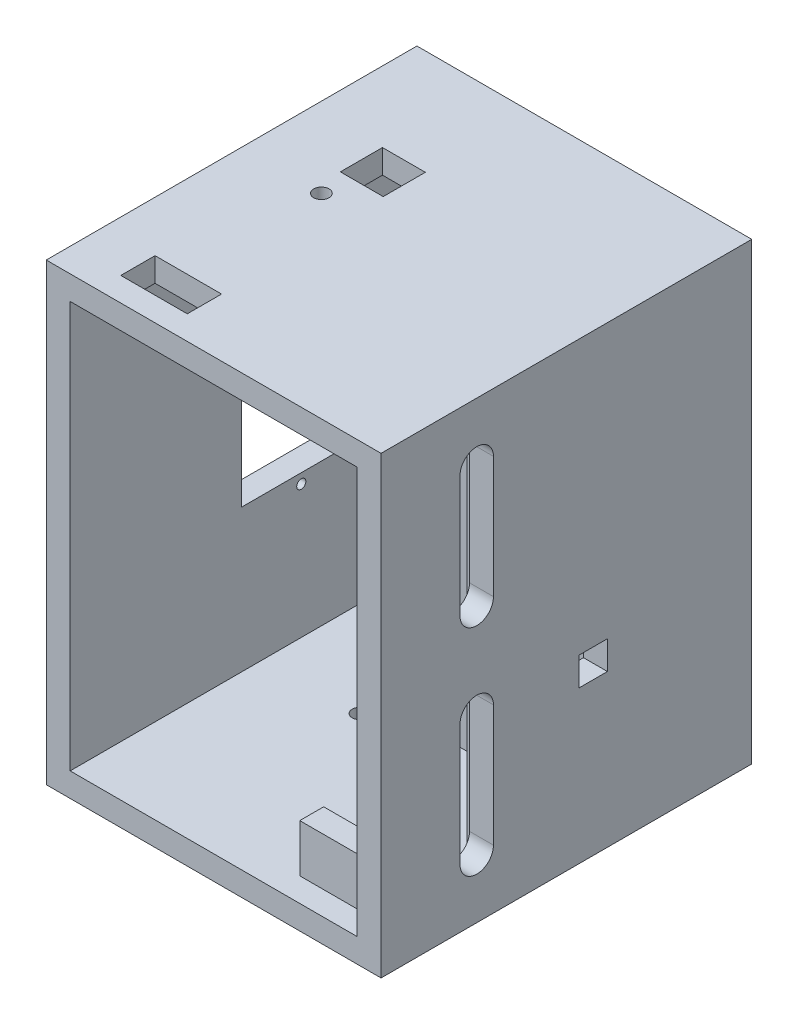
SolidWorks part; units mm, degrees
ref_plane "Front Plane" through (0, 0, 0) normal (0, 0, 1) x (1, 0, 0)
ref_plane "Top Plane" through (0, 0, 0) normal (0, 1, 0) x (1, 0, 0)
ref_plane "Right Plane" through (0, 0, 0) normal (1, 0, 0) x (0, 0, -1)
sketch "Sketch1" plane through (0, 0, 0) normal (0, 0, 1) x (1, 0, 0)
  line L1 (-17.5349, 30.527) -> (52.4651, 30.527)
  line L2 (-17.5349, 30.527) -> (-17.5349, -64.473)
  line L3 (-17.5349, -64.473) -> (52.4651, -64.473)
  line L4 (47.4651, 25.527) -> (-12.5349, 25.527)
  line L5 (-12.5349, 25.527) -> (-12.5349, -59.473)
  line L6 (-12.5349, -59.473) -> (47.4651, -59.473)
  line L7 (47.4651, -59.473) -> (47.4651, 25.527)
  line L8 (47.4651, 25.527) -> (-12.5349, 25.527)
  line L9 (-12.5349, 25.527) -> (-12.5349, -59.473)
  line L10 (-12.5349, -59.473) -> (47.4651, -59.473)
  line L11 (47.4651, -59.473) -> (47.4651, 25.527)
  line L12 (52.4651, 30.527) -> (52.4651, -64.473)
  line L13 (-17.5349, 30.527) -> (52.4651, -64.473) construction
  line L14 (-17.5349, -64.473) -> (52.4651, 30.527) construction
  point P2 (17.4651, -16.973)
  dimension "D2" = 5
  dimension "D3" = 5
  dimension "D4" = 5
  dimension "D5" = 5
  dimension "D1" = 0
extrude "Boss-Extrude1" add sketch "Sketch1" against normal blind 75 contours L12 L1 L2 L3 L11 L10 L9 L8 region at (17.4651, 29.347, 0)
sketch "Sketch2" plane through (-17.5349, 0, 0) normal (-1, 0, 0) x (0, 0, 1)
  line L0 (-59.8109, -17.0822) -> (-59.8109, -28.6392) construction
  line L1 (-60.8109, -29.6392) -> (-35.8239, -29.6392)
  line L2 (-60.8109, -29.6392) -> (-60.8109, -4.5252)
  line L3 (-60.8109, -4.5252) -> (-35.8239, -4.5252)
  line L4 (-35.8239, -29.6392) -> (-35.8239, -4.5252)
  line L5 (-59.8109, -28.6392) -> (-36.8239, -28.6392) construction
  line L6 (-36.8239, -5.5252) -> (-59.8109, -5.5252) construction
  line L7 (-36.8239, -17.0822) -> (-36.8239, -5.5252) construction
  circle A0 centre (-48.3174, -2.4772) radius 0.9525 construction
  circle A1 centre (-48.3174, -31.6872) radius 0.9525 construction
  circle A2 centre (-48.3174, -2.4772) radius 0.9525
  circle A3 centre (-48.3174, -31.6872) radius 0.9525
  dimension "D1" = 1
  dimension "D2" = 1
  dimension "D3" = 1
  dimension "D4" = 1
extrude "Cut-Extrude1" cut sketch "Sketch2" against normal blind 27
sketch "Sketch3" plane through (0, 30.527, 0) normal (0, 1, 0) x (1, 0, 0)
  line L0 (-1.7529, 47.707) -> (5.2067, 47.707) construction
  line L1 (-1.7529, 47.707) -> (5.2067, 47.707)
  line L2 (5.2067, 54.5142) -> (-1.7529, 54.5142) construction
  line L3 (-2.7529, 46.707) -> (6.2067, 46.707)
  line L4 (-2.7529, 46.707) -> (-2.7529, 55.5142)
  line L5 (-2.7529, 55.5142) -> (6.2067, 55.5142)
  line L6 (6.2067, 46.707) -> (6.2067, 55.5142)
  line L7 (-1.7529, 54.5142) -> (-1.7529, 47.707) construction
  line L8 (5.2067, 47.707) -> (5.2067, 54.5142) construction
  line L9 (4.45, 12.1628) -> (-4.45, 12.1628) construction
  line L10 (4.45, 12.1628) -> (-4.45, 12.1628)
  line L11 (47.4651, 0) -> (-12.5349, 0) construction
  line L12 (6.95, 12.1628) -> (-6.95, 12.1628)
  line L13 (6.95, 12.1628) -> (6.95, 5)
  line L14 (6.95, 5) -> (-6.95, 5)
  line L15 (-6.95, 12.1628) -> (-6.95, 5)
  circle A0 centre (-0.8512, 40.8363) radius 1.6129 construction
  circle A1 centre (-0.8512, 40.8363) radius 1.6129
  dimension "D1" = 1
  dimension "D2" = 1
  dimension "D3" = 1
  dimension "D4" = 1
  dimension "D5" = 5
  dimension "D6" = 0
  dimension "D7" = 2.5
  dimension "D8" = 2.5
extrude "Cut-Extrude2" cut sketch "Sketch3" against normal blind 27 contours L3 L6 L5 L4 | A1 | L12 L15 L14 L13 L10 region at (1.7269, 30.527, -51.1106) region at (0, 30.527, -8.5814) region at (-0.8512, 30.527, -40.8363)
sketch "Sketch4" plane through (52.4651, 0, 0) normal (1, 0, 0) x (0, 0, -1)
  line L0 (46.3258, -31.6429) -> (46.3258, -27.7059) construction
  line L1 (47.3258, -32.6429) -> (41.3888, -32.6429)
  line L2 (47.3258, -32.6429) -> (47.3258, -26.7059)
  line L3 (47.3258, -26.7059) -> (41.3888, -26.7059)
  line L4 (41.3888, -32.6429) -> (41.3888, -26.7059)
  line L5 (42.3888, -31.6429) -> (46.3258, -31.6429) construction
  line L6 (46.3258, -27.7059) -> (42.3888, -27.7059) construction
  line L7 (42.3888, -27.7059) -> (42.3888, -31.6429) construction
  dimension "D1" = 1
  dimension "D2" = 1
  dimension "D3" = 1
  dimension "D4" = 1
extrude "Cut-Extrude3" cut sketch "Sketch4" against normal blind 27 contours L3 L4 L1 L2
sketch "Sketch5" plane through (47.4651, 0, 0) normal (-1, 0, 0) x (0, 0, 1)
  line L0 (-38.4772, 5.2125) -> (-38.4772, -47.9243) construction
  line L1 (-5, 25.527) -> (-5, -59.473) construction
  line L2 (-38.4772, 5.2125) -> (-38.4772, -47.9243)
  line L3 (-5, 25.527) -> (-5, -59.473)
  line L5 (-38.4772, -47.9243) -> (-33.4772, -47.9243)
  line L6 (-38.4772, -47.9243) -> (-38.4772, 5.2125)
  line L7 (-38.4772, 5.2125) -> (-33.4772, 5.2125)
  line L8 (-33.4772, -47.9243) -> (-33.4772, 5.2125)
  line L9 (-5, -59.473) -> (-10, -59.473)
  line L10 (-5, -59.473) -> (-5, -49.473)
  line L11 (-5, -49.473) -> (-10, -49.473)
  line L12 (-10, -59.473) -> (-10, -49.473)
  line M8 (-75, -59.473) -> (0, -59.473)
  dimension "D1" = 5
  dimension "D2" = 5
  dimension "D3" = 10
extrude "Boss-Extrude2" add sketch "Sketch5" along normal blind 17 contours L12 L3 L11 M8 | L5 L8 L7 L2 region at (47.4651, -21.3559, -35.9772) region at (47.4651, -54.473, -7.5)
sketch "Sketch6" plane through (0, 0, -38.4772) normal (0, 0, -1) x (-1, 0, 0)
  line L0 (-35.0699, 5.2125) -> (-35.0699, -47.9243) construction
  line L1 (-35.0699, -32.9243) -> (-30.4651, -32.9243)
  line L2 (-35.0699, -32.9243) -> (-35.0699, -9.7875)
  line L3 (-35.0699, -9.7875) -> (-30.4651, -9.7875)
  line L4 (-30.4651, -32.9243) -> (-30.4651, -9.7875)
  line L5 (-30.4651, 5.2125) -> (-30.4651, -47.9243) construction
  line L6 (-30.4651, -47.9243) -> (-47.4651, -47.9243) construction
  line L7 (-30.4651, 5.2125) -> (-47.4651, 5.2125) construction
  dimension "D1" = 15
  dimension "D2" = 15
extrude "Boss-Extrude3" add sketch "Sketch6" along normal blind 17
sketch "Sketch7" plane through (0, 0, -10) normal (0, 0, -1) x (-1, 0, 0)
  circle A0 centre (-43.6551, -55.663) radius 1.27 construction
  circle A1 centre (-43.6551, -55.663) radius 1.27
extrude "Cut-Extrude4" cut sketch "Sketch7" against normal blind 17
sketch "Sketch8" plane through (0, -64.473, 0) normal (0, -1, 0) x (1, 0, 0)
  circle A0 centre (7.3496, -49.5601) radius 5.969 construction
  circle A1 centre (7.3496, -40.6701) radius 1.5875 construction
  circle A2 centre (7.3496, -49.5601) radius 5.969
  circle A3 centre (7.3496, -40.6701) radius 1.5875
  circle A4 centre (7.3496, -49.5601) radius 6.469
  dimension "D1" = 0.5
extrude "Cut-Extrude5" cut sketch "Sketch8" against normal blind 17 contours A2 | A3 region at (7.3496, -64.473, -49.5601) region at (7.3496, -64.473, -40.6701)
sketch "Sketch9" plane through (0, 0, -75) normal (0, 0, -1) x (-1, 0, 0)
  line L4 (-52.4651, 30.527) -> (-52.4651, -64.473)
  line L5 (-52.4651, -64.473) -> (17.5349, -64.473)
  line L6 (17.5349, -64.473) -> (17.5349, 30.527)
  line L7 (17.5349, 30.527) -> (-52.4651, 30.527)
  line L8 (-52.4651, 30.527) -> (-52.4651, -64.473)
  line L9 (-52.4651, -64.473) -> (17.5349, -64.473)
  line L10 (17.5349, -64.473) -> (17.5349, 30.527)
  line L11 (17.5349, 30.527) -> (-52.4651, 30.527)
  dimension "D1" = 0
extrude "Boss-Extrude4" add sketch "Sketch9" along normal mid plane 5
sketch "Sketch10" plane through (0, 0, -77.5) normal (0, 0, -1) x (-1, 0, 0)
  circle A0 centre (-19.6135, 13.0233) radius 4.572 construction
  circle A1 centre (-19.6135, 0.9583) radius 4.572 construction
  circle A2 centre (-19.6135, -11.1067) radius 4.572 construction
  circle A3 centre (-27.3605, -31.6172) radius 1.778 construction
  circle A4 centre (-11.8665, -31.6172) radius 1.778 construction
  circle A5 centre (-19.6135, 13.0233) radius 4.572
  circle A6 centre (-19.6135, 0.9583) radius 4.572
  circle A7 centre (-19.6135, -11.1067) radius 4.572
  circle A8 centre (-27.3605, -31.6172) radius 1.778
  circle A9 centre (-11.8665, -31.6172) radius 1.778
  circle A10 centre (-19.6135, -11.1067) radius 5.572
  circle A11 centre (-19.6135, 0.9583) radius 5.572
  circle A12 centre (-19.6135, 13.0233) radius 5.572
  dimension "D1" = 1
  dimension "D2" = 1
  dimension "D3" = 1
extrude "Cut-Extrude7" cut sketch "Sketch10" against normal blind 24 contours A5 | A12 A5 | A6 | A11 A6 | A9 | A10 | A8 region at (19.6135, 13.0233, -77.5) region at (19.6135, 0.9583, -77.5) region at (11.8665, -31.6172, -77.5) region at (25.0279, 0.9583, -77.5) region at (25.0279, 13.0233, -77.5)
sketch "Sketch11" plane through (52.4651, 0, 0) normal (1, 0, 0) x (0, 0, -1)
  line L0 (20, 18.227) -> (20, -7.173) construction
  line L1 (23.5, 18.227) -> (23.5, -7.173)
  line L2 (16.5, 18.227) -> (16.5, -7.173)
  line L3 (77.5, -16.973) -> (55.4772, -16.973) construction
  line L4 (77.5, 30.527) -> (77.5, -64.473) construction
  line L5 (55.4772, -9.7875) -> (55.4772, -32.9243) construction
  line L6 (0, 30.527) -> (0, -64.473) construction
  line L7 (77.5, 30.527) -> (0, 30.527) construction
  line L8 (20, -52.173) -> (20, -26.773) construction
  line L9 (23.5, -52.173) -> (23.5, -26.773)
  line L10 (16.5, -52.173) -> (16.5, -26.773)
  arc A0 (23.5, 18.227) -> (16.5, 18.227) centre (20, 18.227) ccw
  arc A1 (16.5, -7.173) -> (23.5, -7.173) centre (20, -7.173) ccw
  arc A2 (23.5, -52.173) -> (16.5, -52.173) centre (20, -52.173) cw
  arc A3 (16.5, -26.773) -> (23.5, -26.773) centre (20, -26.773) cw
  point P2 (20, 5.527)
  point P13 (0, 0)
  point P20 (20, -39.473)
  dimension "D1" = 3.5
  dimension "D2" = 25.4
  dimension "D3" = 20
  dimension "D4" = 25
extrude "Cut-Extrude8" cut sketch "Sketch11" against normal blind 10
sketch "Sketch12" plane through (47.4651, 0, 0) normal (-1, 0, 0) x (0, 0, 1)
  line L0 (-72.5, 25.527) -> (0, 25.527) construction
  line L2 (-25.4206, -10.366) -> (-25.4206, 25.527)
  line L3 (-25.4206, 25.527) -> (-30.4206, 25.527)
  line L5 (-72.5, -59.473) -> (-10, -59.473) construction
  line L6 (-30.4206, 25.527) -> (-25.4206, 25.527)
  line L7 (-30.4206, 25.527) -> (-30.4206, -59.473)
  line L8 (-30.4206, -59.473) -> (-25.4206, -59.473)
  line L9 (-25.4206, 25.527) -> (-25.4206, -59.473)
  line L10 (-14.5794, -23.58) -> (-14.5794, -59.473)
  line L12 (-14.5794, -59.473) -> (-9.5794, -59.473)
  line L13 (-14.5794, -59.473) -> (-14.5794, 25.527)
  line L14 (-14.5794, 25.527) -> (-9.5794, 25.527)
  line L15 (-9.5794, -59.473) -> (-9.5794, 25.527)
  line M27 (-72.5, -59.473) -> (-10, -59.473)
  line M28 (-10, -59.473) -> (-10, -49.473)
  line M29 (-10, -49.473) -> (-5, -49.473)
  line M33 (0, 25.527) -> (-72.5, 25.527)
  dimension "D1" = 5
  dimension "D2" = 5
extrude "Boss-Extrude5" add sketch "Sketch12" along normal blind 2.5 contours L9 L2 L7 M33 M27 | L15 L13 L10 M29 M33 M27 M28 region at (47.4651, -16.973, -27.9206) region at (47.4651, -16.5981, -12.1022)
sketch "Sketch14" plane through (-39.2493, -50.7194, -69.6585) normal (-0.4145, -0.5357, -0.7357) x (-0.91, 0.244, 0.3351)
  line L1 (-45.8435, -29.9568) -> (-62.4059, -7.4216)
  line L2 (-45.8435, -29.9568) -> (-4.618, 0.3421)
  line L3 (-62.4059, -7.4216) -> (-21.1804, 22.8773)
  line L4 (-4.618, 0.3421) -> (-21.1804, 22.8773)
  line L5 (-45.8435, -29.9568) -> (-21.1804, 22.8773) construction
  line L6 (-62.4059, -7.4216) -> (-4.618, 0.3421) construction
  point P3 (-33.5119, -3.5398)
extrude "Boss-Extrude6" add sketch "Sketch14" along normal blind 5
sketch "Sketch15" plane through (-41.3219, -53.3978, -73.337) normal (-0.4145, -0.5357, -0.7357) x (-0.91, 0.244, 0.3351)
  circle A0 centre (-20.9554, 16.4362) radius 0.7937 construction
  circle A1 centre (-10.5387, 2.2629) radius 0.7937 construction
  circle A2 centre (-55.2374, -8.7595) radius 0.7938 construction
  circle A3 centre (-44.8207, -22.9328) radius 0.7938 construction
  circle A4 centre (-20.9554, 16.4362) radius 0.7937
  circle A5 centre (-10.5387, 2.2629) radius 0.7937
  circle A6 centre (-55.2374, -8.7595) radius 0.7938
  circle A7 centre (-44.8207, -22.9328) radius 0.7938
extrude "Cut-Extrude10" cut sketch "Sketch15" against normal up to surface (5 mm away) up to face at (-14.2098, -61.8999, -75.6265)
chamfer "Chamfer1" distance 5 angle 45 2 edges at (-17.5349, -60.6133, -74.6897) (-12.5472, -60.6133, -77.5) first distance on face at (-20.179, -41.9036, -86.8227)
